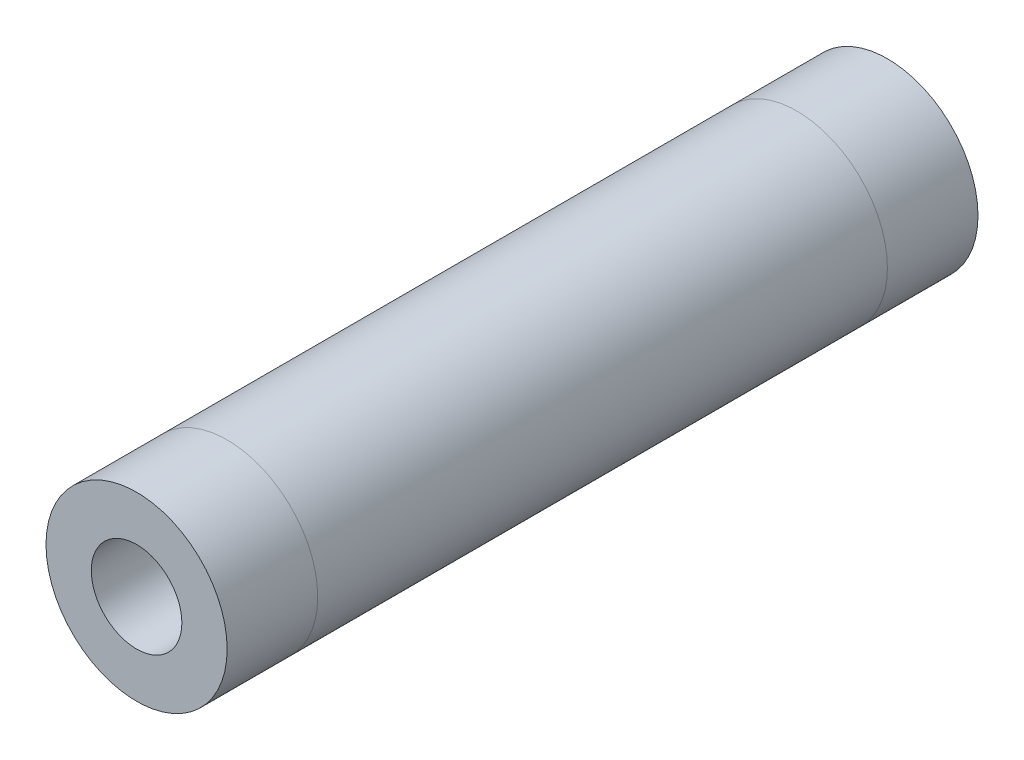
SolidWorks part; units mm, degrees
material "AISI 4130 Steel, normalized at 870C"
ref_plane "Front Plane" through (0, 0, 0) normal (0, 0, 1) x (1, 0, 0)
ref_plane "Top Plane" through (0, 0, 0) normal (0, 1, 0) x (1, 0, 0)
ref_plane "Right Plane" through (0, 0, 0) normal (1, 0, 0) x (0, 0, -1)
sketch "Axis" plane through (0, 0, 0) normal (0, 1, 0) x (1, 0, 0)
  line L0 (0, 0) -> (0, 21.9075) construction
  line L1 (0, 21.9075) -> (0, 74.5457) construction
  line L2 (0, 74.5457) -> (0, 96.4532) construction
  dimension "D1" = 21.9075
  dimension "D2" = 96.4532
sketch "Sketch2" plane through (0, 0, 0) normal (0, 0, 1) x (1, 0, 0)
  circle A0 centre (0, 0) radius 6.35
  circle A1 centre (0, 0) radius 3.175
  circle A2 centre (0, 0) radius 4.7625
  dimension "D1" = 12.7
  dimension "D2" = 6.35
  dimension "D3" = 9.525
extrude "Threaded Insert 1-1" add sketch "Sketch2" against normal blind 6.35 from vertex contours A0 A2 | A2 A1 region at (-6.1704, 0, 0) region at (-4.6278, 0, 0) starting at point (0, 0, -21.9075)
extrude "Threaded Insert 1-2" add sketch "Sketch2<5>" against normal blind 6.35 from surface contours A2 A1 region at (-4.6278, 0, 0) starting at face at (6.35, 0, -28.2575)
sketch "Sketch2<5>" plane through (0, 0, 0) normal (0, 0, 1) x (1, 0, 0) same geometry as "Sketch2"
extrude "Boss-Extrude4" add sketch "Sketch2<7>" along normal blind 6.35 from vertex separate body contours A0 A2 | A2 A1 region at (-6.1704, 0, 0) region at (-4.6278, 0, 0) starting at point (0, 0, -74.5457)
sketch "Sketch2<7>" plane through (0, 0, 0) normal (0, 0, 1) x (1, 0, 0) same geometry as "Sketch2"
extrude "Boss-Extrude5" add sketch "Sketch2<8>" along normal blind 6.35 from surface contours A2 A1 region at (-4.6278, 0, 0) starting at face at (6.35, 0, -68.1957)
sketch "Sketch2<8>" plane through (0, 0, 0) normal (0, 0, 1) x (1, 0, 0) same geometry as "Sketch2"
extrude "Boss-Extrude6" add sketch "Sketch2<9>" against normal up to surface (68.1957 mm away) from surface separate body contours A0 A2 region at (-6.1704, 0, 0) up to face at (6.35, 0, -68.1957) starting at face at (4.7625, 0, -28.2575)
sketch "Sketch2<9>" plane through (0, 0, 0) normal (0, 0, 1) x (1, 0, 0) same geometry as "Sketch2"
equation "\"Tube Outer Diameter\"= .5"
equation "\"Tube Inner Diameter\"= .375"
equation "\"Rod end Diameter\"= .25"
equation "\"Threaded Insert Out\"= .25"
equation "\"Threaded Insert In\"= .25'`"
equation "\"D1@Sketch2\"=\"Tube Outer Diameter\""
equation "\"D2@Sketch2\"=\"Rod end Diameter\""
equation "\"D1@Threaded Insert 1-1\" = \"Threaded Insert Out\""
equation "\"D3@Sketch2\"=\"Tube Inner Diameter\""
equation "\"D1@Threaded Insert 1-2\" = \"Threaded Insert In\""
equation "\"D1@Boss-Extrude4\"=\"Threaded Insert Out\""
equation "\"D1@Boss-Extrude5\"=\"Threaded Insert In\""
